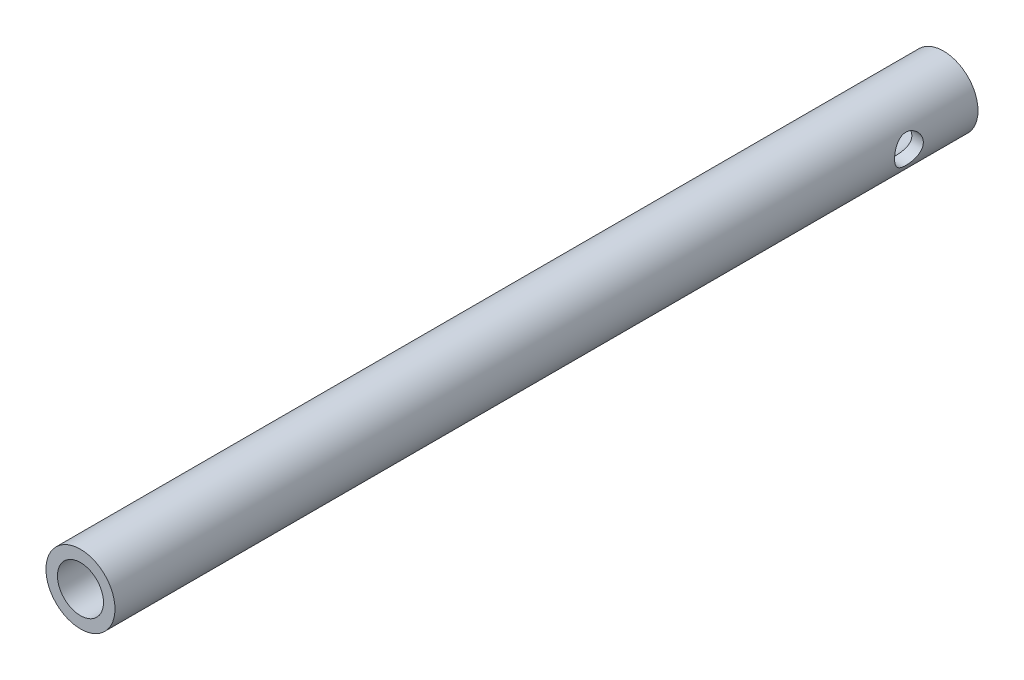
SolidWorks part; units mm, degrees
ref_plane "Front" through (0, 0, 0) normal (0, 0, 1) x (1, 0, 0)
ref_plane "Top" through (0, 0, 0) normal (0, 1, 0) x (1, 0, 0)
ref_plane "Right" through (0, 0, 0) normal (1, 0, 0) x (0, 0, -1)
sketch "Esquisse1" plane through (0, 0, 0) normal (0, 0, 1) x (1, 0, 0)
  circle A0 centre (0, 0) radius 2
  circle A1 centre (0, 0) radius 3
  dimension "D1" = 6
  dimension "D2" = 4
extrude "Boss.-Extru.1" add sketch "Esquisse1" along normal blind 75
sketch "Esquisse2" plane through (0, 0, 0) normal (1, 0, 0) x (0, 0, -1)
  line L0 (0, -3) -> (0, 3) construction
  circle A0 centre (-6, 0) radius 1.25
  dimension "D1" = 2.5
  dimension "D2" = 6
extrude "Enlèv. mat.-Extru.1" cut sketch "Esquisse2" against normal through all both and the other way through all
